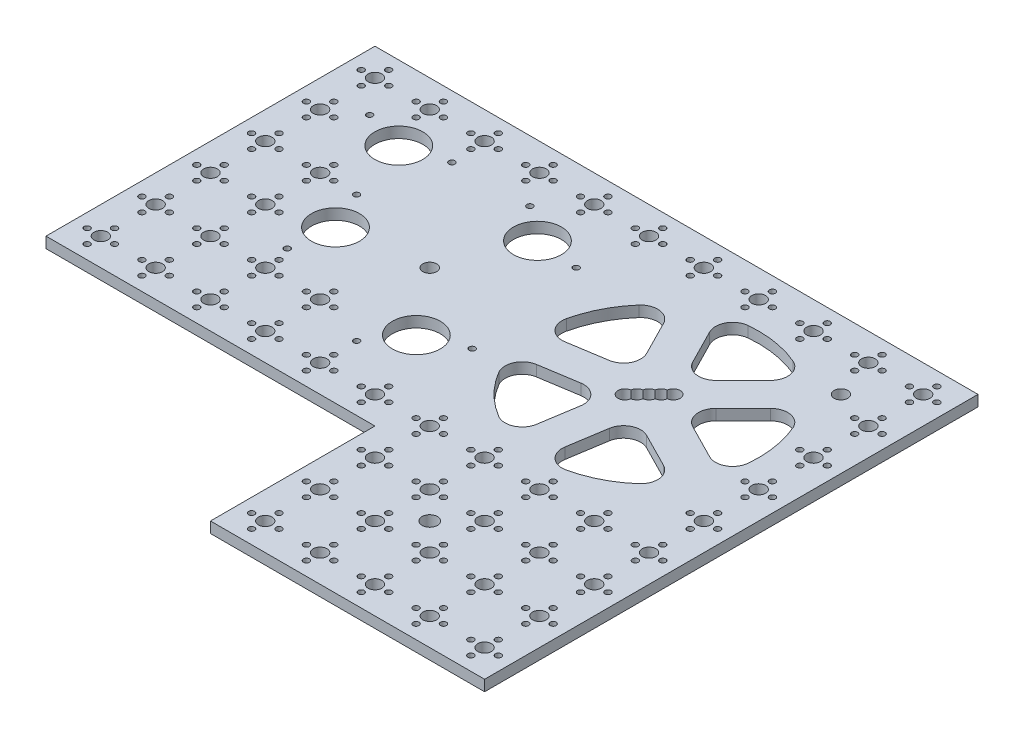
SolidWorks part; units mm, degrees
ref_plane "Front Plane" through (0, 0, 0) normal (0, 0, 1) x (1, 0, 0)
ref_plane "Top Plane" through (0, 0, 0) normal (0, 1, 0) x (1, 0, 0)
ref_plane "Right Plane" through (0, 0, 0) normal (1, 0, 0) x (0, 0, -1)
sketch "Sketch1" plane through (0, 0, 0) normal (0, 1, 0) x (1, 0, 0)
  line L0 (0, 0) -> (0, 128) construction
  line L1 (0, 128) -> (-128, 128) construction
  line L2 (3.5748, 135.2518) -> (-99.4013, 186.0146)
  line L3 (3.5748, 120.7482) -> (-99.4013, 69.9854)
  line L4 (-58.0146, 99.4013) -> (-7.2518, -3.5748)
  line L5 (7.2518, -3.5748) -> (58.0146, 99.4013)
  line L9 (-174.1066, 114.6517) -> (-128, 128) construction
  line L10 (-116.5066, 174.6037) -> (-196.5066, 174.6037) construction
  line L11 (-128, 128) -> (-93.3867, 94.7446) construction
  line L12 (-128, 128) -> (-116.5066, 174.6037) construction
  line L13 (-110.1957, 173.0473) -> (-116.5066, 174.6037) construction
  line L14 (-93.3867, 94.7446) -> (-97.89, 90.0574) construction
  line L15 (-174.1066, 114.6517) -> (-196.5066, 174.6037) construction
  line L16 (-196.5066, 174.6037) -> (-198.7816, 180.6926) construction
  line L17 (-175.9142, 120.8953) -> (-174.1066, 114.6517) construction
  line L18 (-97.89, 90.0574) -> (-98.3966, 96.5376) construction
  line L19 (-196.5066, 174.6037) -> (-194.2316, 168.5148) construction
  line L20 (-174.1066, 114.6517) -> (-170.3137, 119.9303) construction
  circle A0 centre (-174.1066, 114.6517) radius 32
  circle A1 centre (0, 0) radius 8.0851 construction
  circle A2 centre (0, 128) radius 64.6806 construction
  circle A3 centre (0, 128) radius 8.0851 construction
  circle A4 centre (-128, 128) radius 64.6806 construction
  circle A5 centre (-116.5066, 174.6037) radius 32
  circle A6 centre (-93.3867, 94.7446) radius 32
  circle A7 centre (-196.5066, 174.6037) radius 32
  circle A8 centre (0, 0) radius 50
  arc A9 (3.5748, 120.7482) -> (3.5748, 135.2518) centre (0, 128) ccw
  arc A10 (-99.4013, 186.0146) -> (-99.4013, 69.9854) centre (-128, 128) ccw
  arc A11 (-7.2518, -3.5748) -> (7.2518, -3.5748) centre (0, 0) ccw
  arc A12 (-58.0146, 99.4013) -> (58.0146, 99.4013) centre (0, 128) cw
  circle A13 centre (-128, 128) radius 16
  circle A14 centre (-98.3966, 96.5376) radius 27.2
  circle A15 centre (-170.3137, 119.9303) radius 27.0764
  circle A16 centre (-194.2316, 168.5148) radius 27.0764
  dimension "D1" = 16.1701
  dimension "D2" = 129.3611
  dimension "D3" = 32
  dimension "D4" = 64
  dimension "D8" = 100
  dimension "D12" = 54.4
  dimension "D5" = 120
  dimension "D6" = 120
  dimension "D7" = 128
  dimension "D9" = 80
  dimension "D10" = 48
  dimension "D11" = 6.5
sketch "Sketch2" plane through (0, 0, 0) normal (0, 1, 0) x (1, 0, 0)
  line L0 (-256, 224) -> (96, 224)
  line L1 (96, 224) -> (96, -64)
  line L2 (96, -64) -> (-64, -64)
  line L3 (-64, -64) -> (-64, 32)
  line L4 (-64, 32) -> (-256, 32)
  line L5 (-256, 32) -> (-256, 224)
  line L6 (0, 128) -> (-128, 128) construction
  line L8 (0, 0) -> (0, 128) construction
  dimension "D1" = 96
  dimension "D2" = 96
  dimension "D3" = 288
  dimension "D4" = 352
  dimension "D5" = 96
  dimension "D6" = 64
sketch "Sketch3" plane through (0, 0, 0) normal (0, 1, 0) x (1, 0, 0)
  line L0 (-256, 224) -> (-256, 32)
  line L1 (-256, 32) -> (-64, 32)
  line L2 (-64, 32) -> (-64, -64)
  line L3 (-64, -64) -> (96, -64)
  line L4 (96, -64) -> (96, 224)
  line L5 (96, 224) -> (-256, 224)
extrude "Boss-Extrude1" add sketch "Sketch3" along normal blind 6.35
sketch "Sketch4" plane through (0, 6.35, 0) normal (0, 1, 0) x (1, 0, 0)
  line L0 (0, 128) -> (14.1362, 142.1362) construction
  line L1 (-64, -64) -> (96, -64) construction
  circle A0 centre (0, 128) radius 4
  circle A1 centre (-128, 128) radius 4
  circle A2 centre (-198.7816, 180.6926) radius 14
  circle A3 centre (-110.1957, 173.0473) radius 14
  circle A4 centre (-97.89, 90.0574) radius 14
  circle A5 centre (-175.9142, 120.8953) radius 14
  circle A6 centre (0, 0) radius 4.5
  dimension "D1" = 28
  dimension "D2" = 8
  dimension "D3" = 9
  dimension "D4" = 45
extrude "Cut-Extrude1" cut sketch "Sketch4" against normal through all contours A2 | A5 | A3 | A1 | A4 | A6
extrude "Cut-Extrude6" cut sketch "Sketch4<3>" against normal through all contours A0
sketch "Sketch4<3>" plane through (0, 6.35, 0) normal (0, 1, 0) x (1, 0, 0) same geometry as "Sketch4"
pattern_linear "LPattern3" count 3 spacing 5 along (0.7071, 0, -0.7071) count 3 spacing 5 along (-0.7071, 0, 0.7071) of "Cut-Extrude6"
sketch "Sketch5" plane through (0, 6.35, 0) normal (0, 1, 0) x (1, 0, 0)
  line L0 (-198.7816, 180.6926) -> (-198.7816, 187.6926) construction
  line L1 (-175.9142, 120.8953) -> (-182.8385, 119.8686) construction
  line L2 (-97.89, 90.0574) -> (-93.5387, 84.5742) construction
  line L3 (-110.1957, 173.0473) -> (-107.6228, 179.5573) construction
  line L5 (-186.3587, 143.609) -> (-179.3183, 96.1281) construction
  line L6 (-112.3384, 69.6553) -> (-74.739, 99.493) construction
  line L7 (-129.9427, 188.3789) -> (-85.3028, 170.7356) construction
  line L9 (-174.7816, 187.6926) -> (-222.7816, 187.6926) construction
  circle A0 centre (-222.7816, 187.6926) radius 1.75
  circle A1 centre (-174.7816, 187.6926) radius 1.75
  circle A2 centre (-129.9427, 188.3789) radius 1.75
  circle A3 centre (-85.3028, 170.7356) radius 1.75
  circle A4 centre (-74.739, 99.493) radius 1.75
  circle A5 centre (-112.3384, 69.6553) radius 1.75
  circle A6 centre (-179.3183, 96.1281) radius 1.75
  circle A7 centre (-186.3587, 143.609) radius 1.75
  dimension "D3" = 3.5
  dimension "D1" = 48
  dimension "D2" = 7
extrude "Cut-Extrude2" cut sketch "Sketch5" against normal through all
sketch "Sketch6" plane through (0, 6.35, 0) normal (0, 1, 0) x (1, 0, 0)
  line L0 (-19.7885, 188.8639) -> (2.6614, 144.8036)
  line L1 (2.6614, 144.8036) -> (37.6279, 179.7701)
  line L4 (-141421.3562, -141293.3562) -> (141435.4925, 141563.4925) construction
  arc A0 (-19.7885, 188.8639) -> (37.6279, 179.7701) centre (0, 128) cw
  point P19 (0, 128)
  dimension "D1" = 10
  dimension "D2" = 64
  dimension "D3" = 10
  dimension "D4" = 72
extrude "Cut-Extrude3" cut sketch "Sketch6" against normal through all
fillet "Fillet2" radius 10 3 edges at (2.6614, 3.175, -144.8036) (-19.7885, 3.175, -188.8639) (37.6279, 3.175, -179.7701)
pattern_circular "CirPattern2" count 5 over 360 about axis through (0, 0, -128) along (0, 1, 0) of "Fillet2", "Cut-Extrude3"
sketch "Sketch7" plane through (0, 6.35, 0) normal (0, 1, 0) x (1, 0, 0)
  line L0 (96, 208) -> (80, 208) construction
  line L1 (96, -64) -> (96, 224) construction
  line L2 (96, 224) -> (-256, 224) construction
  circle A0 centre (80, 208) radius 4
  point P26 (80, 208)
  dimension "D2" = 8
  dimension "D1" = 16
  dimension "D5" = 16
extrude "Cut-Extrude4" cut sketch "Sketch7" against normal through all
sketch "Sketch10" plane through (0, 6.35, 0) normal (0, 1, 0) x (1, 0, 0)
  line L0 (80, 208) -> (88, 208) construction
  circle A0 centre (88, 208) radius 1.75
  circle A1 centre (80, 200) radius 1.75
  circle A2 centre (72, 208) radius 1.75
  circle A3 centre (80, 216) radius 1.75
  point P13 (80, 208)
  dimension "D2" = 3.5
  dimension "D1" = 8
  dimension "D3" = 4
extrude "Cut-Extrude5" cut sketch "Sketch10" against normal through all
pattern_linear "LPattern1" count 11 spacing 32 along (-1, 0, 0) count 9 spacing 32 along (0, 0, 1) skipping (1, 1), (1, 2), (1, 3), (1, 4), (2, 1), (2, 2), (2, 3), (2, 4), (3, 1), (3, 2), (3, 3), (3, 4), (4, 1), (4, 2), (4, 3), (4, 4), (5, 1), (5, 2), (5, 3), (5, 4), (6, 1), (6, 2), (6, 3), (6, 4), (7, 1), (7, 2), (7, 3), (8, 1), (8, 2), (8, 3), (9, 1) of "Cut-Extrude4"
pattern_linear "LPattern2" count 11 spacing 32 along (-1, 0, 0) count 9 spacing 32 along (0, 0, 1) skipping (1, 1), (1, 2), (1, 3), (1, 4), (2, 1), (2, 2), (2, 3), (2, 4), (3, 1), (3, 2), (3, 3), (3, 4), (4, 1), (4, 2), (4, 3), (4, 4), (5, 1), (5, 2), (5, 3), (5, 4), (6, 1), (6, 2), (6, 3), (6, 4), (7, 1), (7, 2), (7, 3), (8, 1), (8, 2), (8, 3), (9, 1) of "Cut-Extrude5"
sketch "Sketch12" plane through (0, 6.35, 0) normal (0, 1, 0) x (1, 0, 0)
  line L0 (-141421.3562, -141293.3562) -> (141435.4925, 141563.4925) construction
  line L1 (96, -64) -> (96, 224) construction
  circle A0 centre (56, 184) radius 4
  circle A1 centre (80, 208) radius 4 construction
  dimension "D1" = 40
extrude "Cut-Extrude8" cut sketch "Sketch12" against normal through all
equation "\"D1@Sketch1\"=10*5.08/PI"
equation "\"D2@Sketch1\"=80*5.08/PI"
